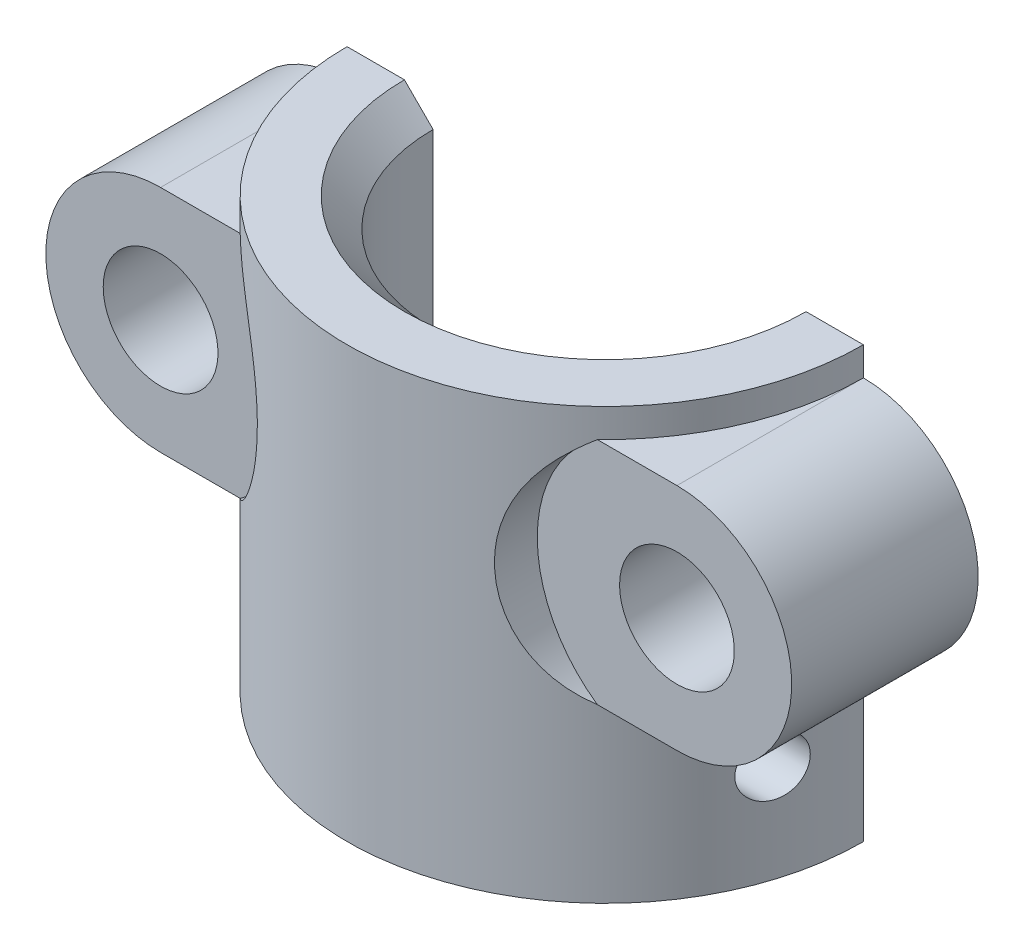
SolidWorks part; units mm, degrees
ref_plane "Planta" through (0, 0, 0) normal (0, 0, 1) x (1, 0, 0)
ref_plane "Alzado" through (0, 0, 0) normal (0, 1, 0) x (1, 0, 0)
ref_plane "Vista lateral" through (0, 0, 0) normal (1, 0, 0) x (0, 0, -1)
sketch "Croquis2" plane through (0, 0, 0) normal (0, 0, 1) x (1, 0, 0)
  line L0 (6.0668, 7.6358) -> (6.0668, -7.3642)
  line L1 (6.0668, 7.6358) -> (9.0668, 7.6358)
  line L2 (9.0668, 7.6358) -> (9.0668, 6.6358)
  line L3 (9.0668, -7.3642) -> (6.0668, -7.3642)
  line L4 (9.0668, 7.6358) -> (9.0668, 6.6358)
  line L5 (9.0668, -1.3642) -> (9.0668, -7.3642)
  line L6 (0.0668, -10.4803) -> (0.0668, 10.2151) construction
  line L7 (-8.9332, -1.3642) -> (-8.9332, -7.3642)
  line L8 (-8.9332, 7.6358) -> (-8.9332, 6.6358)
  line L9 (-8.9332, -7.3642) -> (-5.9332, -7.3642)
  line L10 (-8.9332, 7.6358) -> (-8.9332, 6.6358)
  line L11 (-5.9332, 7.6358) -> (-8.9332, 7.6358)
  line L12 (-5.9332, 7.6358) -> (-5.9332, -7.3642)
  circle A0 centre (9.0668, 2.6358) radius 2
  arc A1 (9.0668, -1.3642) -> (9.0668, 6.6358) centre (9.0668, 2.6358) ccw
  arc A2 (-8.9332, -1.3642) -> (-8.9332, 6.6358) centre (-8.9332, 2.6358) cw
  circle A3 centre (-8.9332, 2.6358) radius 2
  dimension "D4" = 4
  dimension "D7" = 4
  dimension "D1" = 15
  dimension "D2" = 3
  dimension "D3" = 5
  dimension "D5" = 9
  dimension "D6" = 9
extrude "Saliente-Extruir1" add sketch "Croquis2" along normal blind 6.5 contours A2 L7 L9 L12 L11 L8 A3 | L5 A1 L2 L1 L0 L3 A0 region at (8.6354, 0.6816, 0) region at (-8.5018, 0.6816, 0)
sketch "Croquis3" plane through (0, -7.3642, 0) normal (0, -1, 0) x (1, 0, 0)
  line L0 (-8.9332, 0) -> (-5.9332, 0)
  line L1 (9.0668, 6.5) -> (9.0668, 0) construction
  line L2 (9.0668, 0) -> (6.0668, 0) construction
  line L3 (6.0668, 0) -> (9.0668, 0)
  arc A0 (9.0668, 0) -> (-8.9332, 0) centre (0.0668, 0) ccw
  arc A1 (6.0668, 0) -> (-5.9332, 0) centre (0.0668, 0) ccw
extrude "Saliente-Extruir2" add sketch "Croquis3" against normal through all
sketch "Croquis7" plane through (0, 0, 6.5) normal (0, 0, 1) x (1, 0, 0)
  circle A0 centre (9.0668, 2.6358) radius 2
  circle A1 centre (-8.9332, 2.6358) radius 2
extrude "Cortar-Extruir3" cut sketch "Croquis7" against normal blind 7
sketch "Croquis12" plane through (0, 0, 6.5) normal (0, 0, 1) x (1, 0, 0)
  line L2 (6.2918, -7.3642) -> (9.0668, -7.3642)
  line L3 (6.2918, -7.3642) -> (6.2918, -1.3642)
  line L4 (6.2918, -1.3642) -> (9.0668, -1.3642)
  line L6 (9.0668, 6.6358) -> (6.2918, 6.6358)
  line L7 (9.0668, 6.6358) -> (9.0668, 7.6358)
  line L8 (9.0668, 7.6358) -> (6.2918, 7.6358)
  line L9 (6.2918, 6.6358) -> (6.2918, 7.6358)
  line L10 (-8.9332, 6.6358) -> (-6.1581, 6.6358)
  line L11 (-8.9332, 6.6358) -> (-8.9332, 7.6358)
  line L12 (-8.9332, 7.6358) -> (-6.1581, 7.6358)
  line L13 (-6.1581, 6.6358) -> (-6.1581, 7.6358)
  line L14 (9.0668, -7.3642) -> (9.0668, -1.3642)
  line L15 (-8.9332, -1.3642) -> (-6.1581, -1.3642)
  line L16 (-8.9332, -1.3642) -> (-8.9332, -7.3642)
  line L17 (-8.9332, -7.3642) -> (-6.1581, -7.3642)
  line L18 (-6.1581, -1.3642) -> (-6.1581, -7.3642)
extrude "Cortar-Extruir5" cut sketch "Croquis12" against normal up to surface up to face at (0.0668, 0.1358, 7.75)
sketch "Croquis13" plane through (0, 0, 6.5) normal (0, 0, 1) x (1, 0, 0)
  circle A0 centre (9.0668, 2.6358) radius 4.8684
  circle A1 centre (-8.9332, 2.6358) radius 4.8684
extrude "Cortar-Extruir6" cut sketch "Croquis13" along normal blind 4
chamfer "Chaflán1" distance 1 angle 45 2 edges at (0.0668, 7.6358, 6) (0.0668, -7.3642, 6)
ref_plane "Plano2" through (9.0668, 0, 0) normal (-1, 0, 0) x (0, -1, 0)
sketch "Croquis14" plane through (9.0668, 0, 0) normal (-1, 0, 0) x (0, -1, 0)
  circle A0 centre (3.9567, 2.6923) radius 1
  dimension "D1" = 2
extrude "Cortar-Extruir7" cut sketch "Croquis14" along normal up to surface (4.2706 mm away) up to face at (0.0668, 0.1358, 3)
